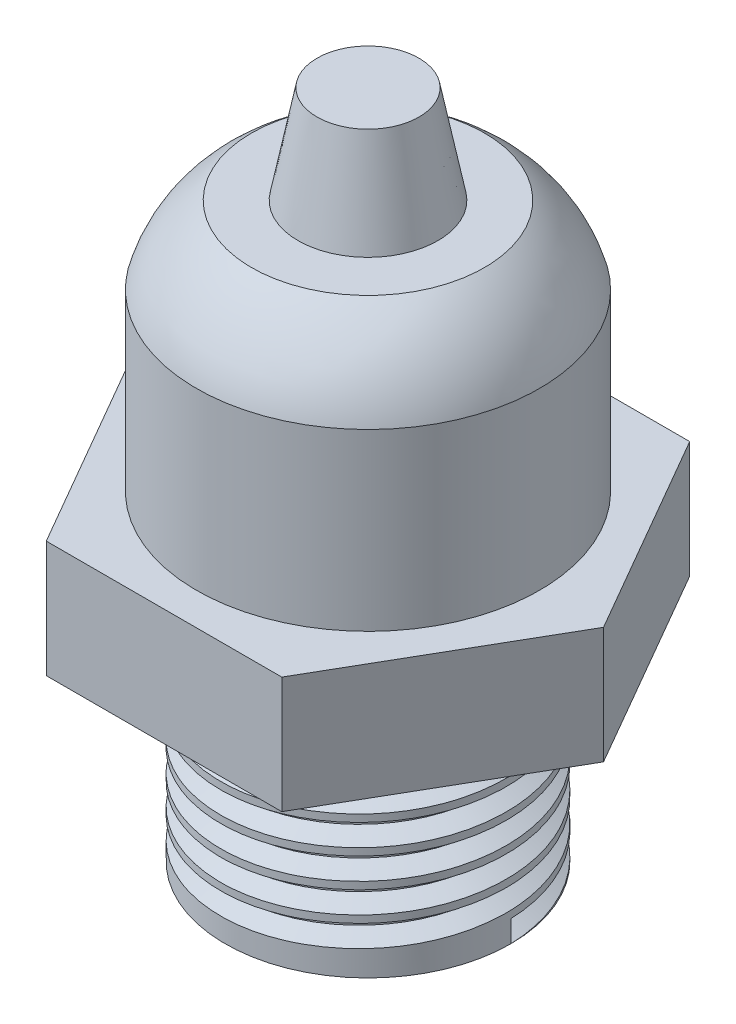
SolidWorks part; units mm, degrees
ref_plane "Front Plane" through (0, 0, 0) normal (0, 0, 1) x (1, 0, 0)
ref_plane "Top Plane" through (0, 0, 0) normal (0, 1, 0) x (1, 0, 0)
ref_plane "Right Plane" through (0, 0, 0) normal (1, 0, 0) x (0, 0, -1)
sketch "Sketch1" plane through (0, 0, 0) normal (0, 1, 0) x (1, 0, 0)
  line L1 (8.0829, 0) -> (4.0415, 7)
  line L2 (4.0415, 7) -> (-4.0415, 7)
  line L3 (-4.0415, 7) -> (-8.0829, 0)
  line L4 (-8.0829, 0) -> (-4.0415, -7)
  line L5 (-4.0415, -7) -> (4.0415, -7)
  line L6 (4.0415, -7) -> (8.0829, 0)
  circle A0 centre (0, 0) radius 7 construction
  dimension "D1" = 14
extrude "Boss-Extrude1" add sketch "Sketch1" along normal blind 4
sketch "Sketch3" plane through (0, 0, 0) normal (0, 0, 1) x (1, 0, 0)
  line L0 (0, 4) -> (0, 16) construction
  line L1 (-4.0415, 4) -> (4.0415, 4) construction
  line L2 (0, 16) -> (1.75, 16)
  line L3 (1.75, 16) -> (2.4, 12.65)
  line L4 (2.4, 12.65) -> (0, 12.65) construction
  line L5 (2.4, 12.65) -> (4, 12.65)
  line L6 (5.8875, 4) -> (5.8875, 10)
  line L7 (4.0415, 4) -> (8.0829, 4) construction
  line L8 (0, 16) -> (0, 4)
  line L9 (0, 4) -> (5.8875, 4)
  arc A0 (4, 12.65) -> (5.8875, 10) centre (1.3088, 8.7359) cw
  dimension "D8" = 4.75
  dimension "D1" = 12
  dimension "D2" = 1.75
  dimension "D3" = 3.35
  dimension "D4" = 2.4
  dimension "D5" = 4
  dimension "D6" = 5.8875
  dimension "D7" = 6
revolve "Revolve1" add sketch "Sketch3" angle 360 about L8 region at (2.6283, 8.9395, 0)
sketch "Sketch4" plane through (0, 0, 0) normal (0, -1, 0) x (1, 0, 0)
  line L0 (3.55, 0) -> (4.9, 0) construction
  circle A0 centre (0, 0) radius 4.9
  circle A1 centre (0, 0) radius 3.55
  dimension "D2" = 9.8
  dimension "D1" = 1.35
extrude "Boss-Extrude3" add sketch "Sketch4" along normal blind 7
thread "Thread1" pitch 1 method cut profile "Thread Profile1" start angle 0, offset 0, length 0, pitch 1, diameter 9.8
ref_plane "Plane1" through (4.9, -7, 0) normal (0, 0, -1) x (-1, 0, 0)
sketch "Thread Profile1" plane through (4.9, -7, 0) normal (0, 0, -1) x (-1, 0, 0)
  line L0 (0, 0) -> (0, 1) construction
  line L1 (0, 0) -> (0.5413, 0.3125)
  line L2 (0.5413, 0.3125) -> (0.5413, 0.4375)
  line L3 (0.5413, 0.4375) -> (0, 0.75)
  line L4 (0.5413, 0.375) -> (0, 0.375) construction
  line L11 (0, 0) -> (0, 0.75)
  point P2 (0, 0)
  dimension "Pitch" = 1
  dimension "Profile_Angle" = 60
  dimension "Profile_Land" = 0.125
  dimension "Profile_Height" = 0.5413
sketch "Sketch8" plane through (0, 0, 0) normal (0, -1, 0) x (1, 0, 0)
  circle A0 centre (0, 0) radius 1
  dimension "D1" = 2
extrude "Boss-Extrude4" add sketch "Sketch8" along normal up to surface (7 mm away) up to face at (0, -7, -4.9)
